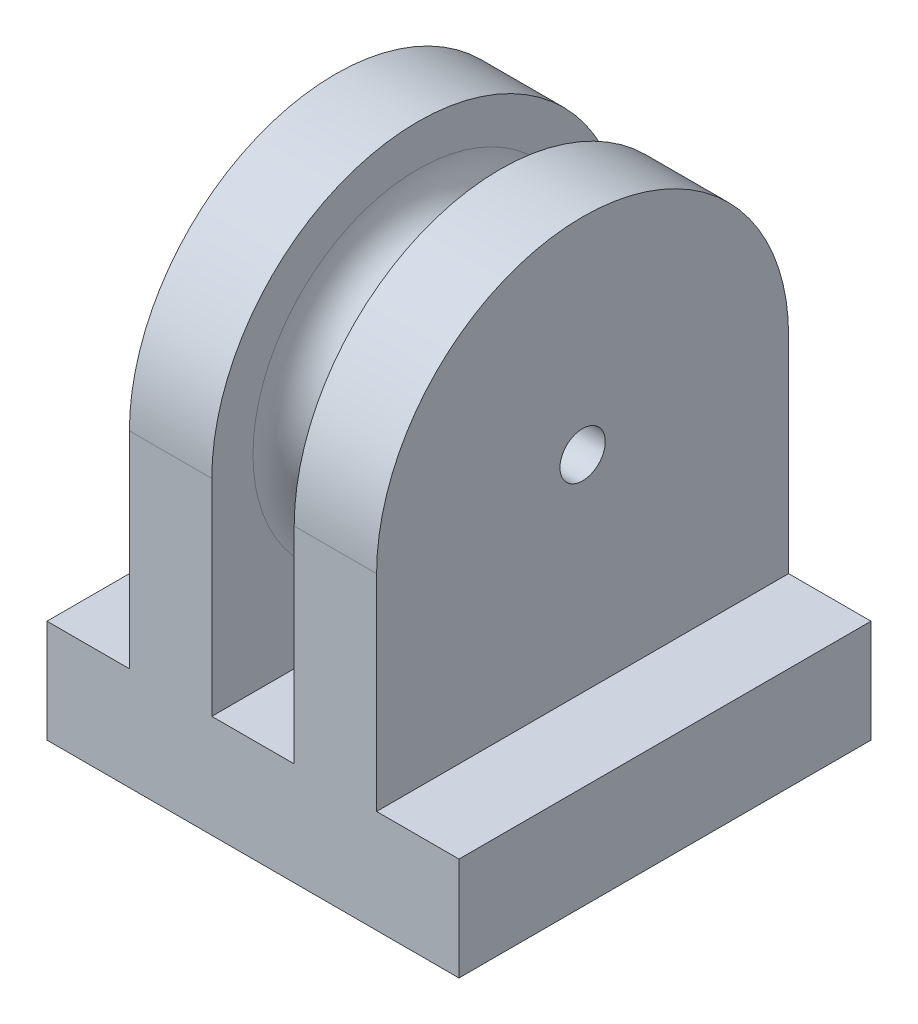
SolidWorks part; units mm, degrees
ref_plane "Front Plane" through (0, 0, 0) normal (0, 0, 1) x (1, 0, 0)
ref_plane "Top Plane" through (0, 0, 0) normal (0, 1, 0) x (1, 0, 0)
ref_plane "Right Plane" through (0, 0, 0) normal (1, 0, 0) x (0, 0, -1)
sketch "Sketch1" plane through (0, 0, 0) normal (0, 1, 0) x (1, 0, 0)
  line L1 (0, 0) -> (20, 0)
  line L2 (0, 0) -> (0, 20)
  line L3 (0, 20) -> (20, 20)
  line L4 (20, 0) -> (20, 20)
  dimension "D1" = 20
  dimension "D2" = 20
extrude "Boss-Extrude1" add sketch "Sketch1" along normal blind 5
sketch "Sketch3" plane through (0, 5, 0) normal (0, 1, 0) x (1, 0, 0)
  line L0 (20, 20) -> (0, 20) construction
  line L1 (4, 20) -> (8, 20)
  line L2 (4, 20) -> (4, 0)
  line L3 (4, 0) -> (8, 0)
  line L4 (8, 20) -> (8, 0)
  line L5 (0, 0) -> (20, 0) construction
  line L6 (0, 20) -> (0, 0) construction
  line L7 (12, 20) -> (16, 20)
  line L8 (12, 20) -> (12, 0)
  line L9 (12, 0) -> (16, 0)
  line L10 (16, 20) -> (16, 0)
  line L11 (20, 0) -> (20, 20) construction
  dimension "D1" = 4
  dimension "D2" = 4
  dimension "D3" = 4
  dimension "D4" = 4
extrude "Boss-Extrude2" add sketch "Sketch3" along normal blind 10
sketch "Sketch4" plane through (4, 0, 0) normal (-1, 0, 0) x (0, 0, 1)
  line L0 (-20, 15) -> (0, 15) construction
  circle A0 centre (-10, 15) radius 10
extrude "Boss-Extrude3" add sketch "Sketch4" against normal blind 4
sketch "Sketch5" plane through (16, 0, 0) normal (1, 0, 0) x (0, 0, -1)
  line L0 (0, 15) -> (20, 15) construction
  circle A0 centre (10, 15) radius 10
extrude "Boss-Extrude4" add sketch "Sketch5" against normal blind 4
sketch "Sketch6" plane through (4, 0, 0) normal (-1, 0, 0) x (0, 0, 1)
  line L1 (-20, 5) -> (0, 5) construction
  line L3 (-20, 15) -> (-20, 5) construction
  circle A0 centre (-10, 15) radius 1.1
  point P3 (0, 0)
  point P8 (-20, 11.4626)
  dimension "D1" = 2.2
  dimension "D2" = 10
  dimension "D3" = 10
extrude "Cut-Extrude1" cut sketch "Sketch6" against normal through all
sketch "Sketch7" plane through (0, 5, 0) normal (0, 1, 0) x (1, 0, 0)
  line L0 (8, 0) -> (12, 0) construction
  line L1 (8, 0) -> (8, 20) construction
  line L2 (0, 10) -> (20, 10) construction
  line L3 (0, 20) -> (0, 0) construction
  line L4 (20, 0) -> (20, 20) construction
  circle A0 centre (10, 4) radius 0.5
  circle A1 centre (10, 16) radius 0.5
  dimension "D1" = 1
  dimension "D2" = 4
  dimension "D3" = 2
extrude "Cut-Extrude2" cut sketch "Sketch7" against normal through all
sketch "Sketch9" plane through (8, 0, 0) normal (1, 0, 0) x (0, 0, -1)
  circle A0 centre (10, 15) radius 6
  dimension "D1" = 12
extrude "Boss-Extrude5" add sketch "Sketch9" along normal blind 4
sketch "Sketch10" plane through (8, 0, 0) normal (1, 0, 0) x (0, 0, -1)
  line L0 (20, 5) -> (0, 5) construction
  line L1 (20, 15) -> (20, 5) construction
  circle A0 centre (10, 15) radius 1.1
  point P3 (0, 0)
  dimension "D1" = 2.2
  dimension "D2" = 10
  dimension "D3" = 10
extrude "Cut-Extrude3" cut sketch "Sketch10" along normal blind 4
fillet "Fillet1" radius 2 2 edges at (8, 15, -4) (12, 15, -16)
